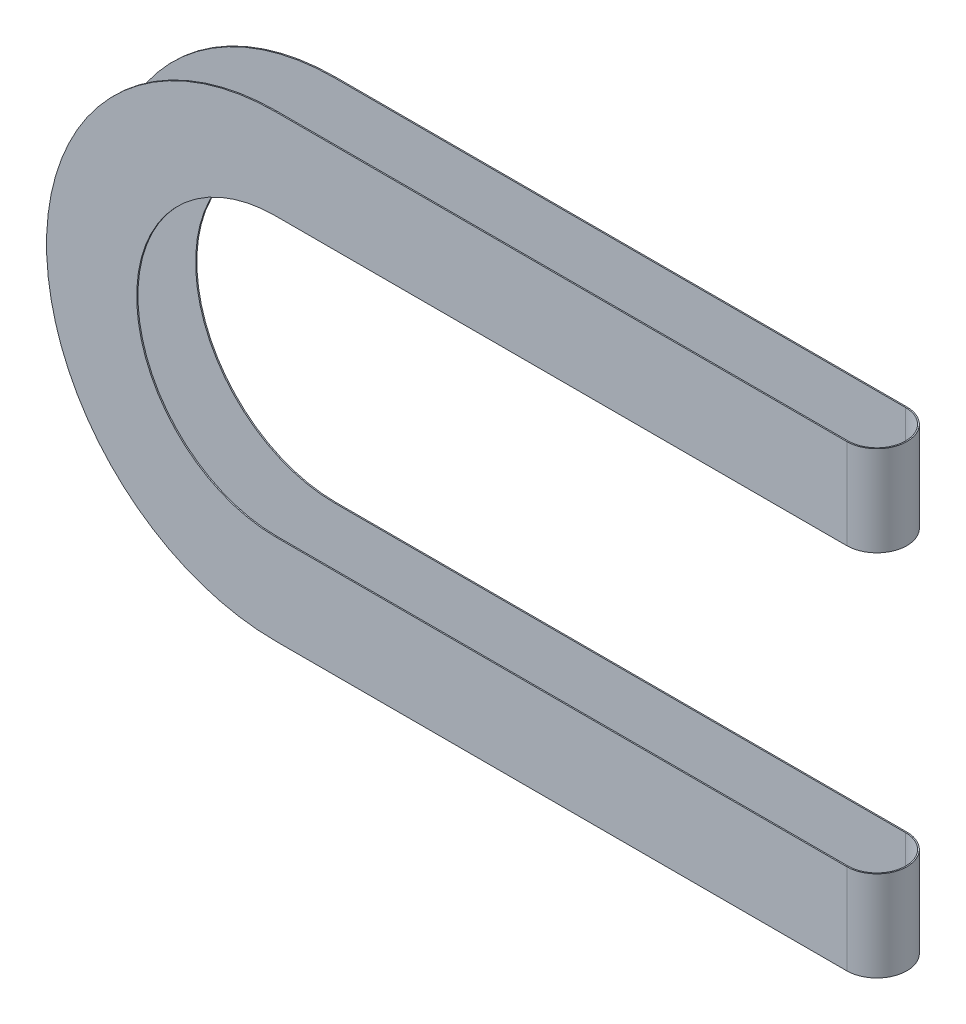
SolidWorks part; units mm, degrees
ref_plane "前视基准面" through (0, 0, 0) normal (0, 0, 1) x (1, 0, 0)
ref_plane "上视基准面" through (0, 0, 0) normal (0, 1, 0) x (1, 0, 0)
ref_plane "右视基准面" through (0, 0, 0) normal (1, 0, 0) x (0, 0, -1)
other "Configuration Table"
sketch "草图1" plane through (0, 0, 0) normal (0, 0, 1) x (1, 0, 0)
  line L0 (0, -56.25) -> (0, 306.25)
  line L1 (0, -56.25) -> (0, -418.75)
  line L2 (0, 306.25) -> (1230.231, 306.25)
  line L3 (0, -306.25) -> (1230.231, -306.25)
  line L4 (0, 391.25) -> (1000, 391.25)
  line L9 (0, 211.25) -> (1000, 231.25) construction
  line L10 (0, 231.25) -> (1000, 211.25) construction
  line L15 (230.231, -221.25) -> (769.769, -221.25)
  line L16 (0, -231.25) -> (1000, -231.25)
  line L17 (0, 381.25) -> (1000, 381.25)
  line L18 (0, 381.25) -> (0, 401.25)
  line L19 (0, 401.25) -> (1000, 401.25)
  line L20 (1000, 381.25) -> (1000, 401.25)
  line L21 (0, 381.25) -> (1000, 401.25) construction
  line L22 (0, 401.25) -> (1000, 381.25) construction
  line L23 (1000, 231.25) -> (1000, 211.25)
  line L24 (0, 211.25) -> (1000, 211.25)
  line L25 (0, 231.25) -> (0, 211.25)
  line L26 (0, 231.25) -> (1000, 231.25)
  line L27 (0, 221.25) -> (1000, 221.25)
  line L28 (0, -231.25) -> (0, -211.25)
  line L29 (0, -211.25) -> (1000, -211.25)
  line L30 (1000, -231.25) -> (1000, -211.25)
  line L31 (0, -231.25) -> (1000, -211.25) construction
  line L32 (0, -211.25) -> (1000, -231.25) construction
  line L33 (0, -401.25) -> (1000, -381.25) construction
  line L34 (0, -381.25) -> (1000, -401.25) construction
  line L35 (1000, -381.25) -> (1000, -401.25)
  line L36 (0, -401.25) -> (1000, -401.25)
  line L37 (0, -381.25) -> (0, -401.25)
  line L38 (0, -381.25) -> (1000, -381.25)
  line L39 (230.231, -391.25) -> (769.769, -391.25)
  line L40 (1000, 381.25) -> (1000, 231.25)
  line L41 (1000, -231.25) -> (1000, -381.25)
  circle A0 centre (0, -56.25) radius 250 construction
  circle A1 centre (0, -56.25) radius 362.5 construction
  arc A2 (0, 211.25) -> (0, -211.25) centre (0, 0) ccw
  arc A3 (0, -231.25) -> (0, 231.25) centre (0, 0) cw
  arc A5 (0, -381.25) -> (0, 381.25) centre (0, 0) cw
  arc A6 (0, -401.25) -> (0, 401.25) centre (0, 0) cw
  point P14 (500, -221.25)
  point P19 (500, 391.25)
  point P27 (500, 221.25)
  point P36 (500, -391.25)
  dimension "D1" = 500
  dimension "D2" = 725
  dimension "D3" = 75
  dimension "D4" = 20
  dimension "D5" = 1000
  dimension "D6" = 1000
  dimension "D7" = 75
  dimension "D8" = 1000
  dimension "D9" = 150
  dimension "D10" = 20
  dimension "D11" = 1000
extrude "凸台-拉伸1" add sketch "草图1" along normal blind 100 contours A5 L1 A3 L0 L2 L40 L17 | L40 L2 L0 L26 | L41 L16 L1 L3 | L41 L3 L1 L38 region at (500, -268.75, 0) region at (-15.7774, -268.75, 0) region at (500, 268.75, 0) region at (500, -343.75, 0)
sketch "草图2" plane through (0, -381.25, 0) normal (0, -1, 0) x (1, 0, 0)
  line L0 (0, 100) -> (1000, 100) construction
  line L1 (-399.7778, 98) -> (950, 98)
  line L2 (-399.7778, 98) -> (-399.7778, 2)
  line L3 (-399.7778, 2) -> (950, 2)
  line L4 (950, 98) -> (950, 2)
  line L5 (0, 0) -> (1000, 0) construction
  line L7 (1000, 100) -> (1000, 0) construction
  circle A0 centre (950, 50) radius 48
  circle A2 centre (950, 50) radius 50
  line M5 (0, 0) -> (1000, 0)
  line M6 (1000, 0) -> (1000, 100)
  line M7 (1000, 100) -> (0, 100)
  line M8 (0, 100) -> (0, 0)
  dimension "D4" = 96
  dimension "D1" = 2
  dimension "D2" = 2
  dimension "D3" = 96
  dimension "D5" = 50
  dimension "D6" = 2
extrude "切除-拉伸1" cut sketch "草图2" against normal blind 1000 contours L2 L3 L1 M8 | A2 L1 L3 M8 | L1 A2 L3 A0 | L4 A0 | L4 A0 | A2 M6 M7 | A2 M5 M6 region at (-199.8889, -381.25, 50) region at (454.7919, -381.25, 50) region at (943, -381.25, 97.8918) region at (970.3718, -381.25, 50) region at (929.6282, -381.25, 50) region at (988.8316, -381.25, 88.8316) region at (988.8316, -381.25, 11.1684)
